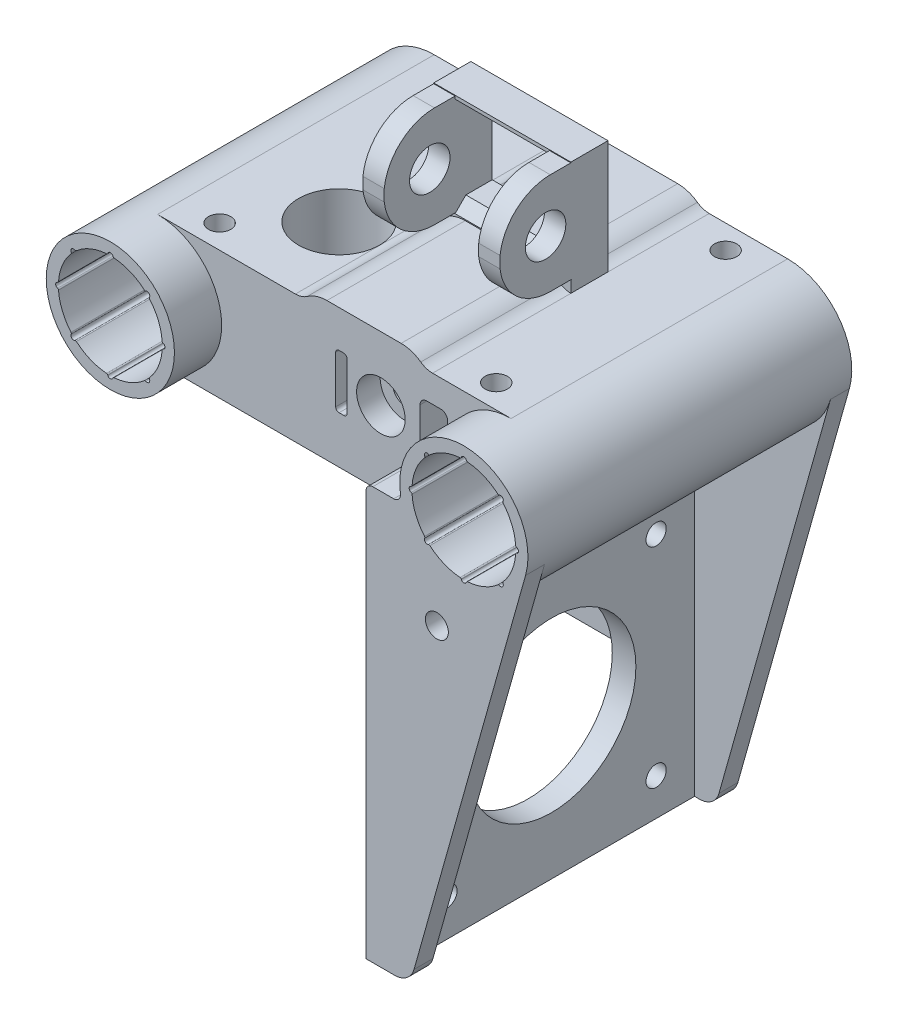
SolidWorks part; units mm, degrees
material "PET"
ref_plane "Front Plane" through (0, 0, 0) normal (0, 0, 1) x (1, 0, 0)
ref_plane "Top Plane" through (0, 0, 0) normal (0, 1, 0) x (1, 0, 0)
ref_plane "Right Plane" through (0, 0, 0) normal (1, 0, 0) x (0, 0, -1)
sketch "Sketch1" plane through (0, 0, 0) normal (0, 0, 1) x (1, 0, 0)
  arc A14 (-5.825, 5.0358) -> (-7.6797, 0.5581) centre (0, 0) ccw
  arc A15 (46.575, 5.0358) -> (44.7203, 0.5581) centre (52.4, 0) ccw
  circle A16 centre (0, 0) radius 9.5
  circle A17 centre (52.4, 0) radius 9.5
  arc A18 (-7.8195, 0.3817) -> (-7.8195, -0.3817) centre (-7.7, 0) ccw
  arc A19 (-5.2593, 5.7991) -> (-5.7991, 5.2593) centre (-5.4447, 5.4447) ccw
  arc A20 (0.3817, 7.8195) -> (-0.3817, 7.8195) centre (0, 7.7) ccw
  arc A21 (5.7991, 5.2593) -> (5.2593, 5.7991) centre (5.4447, 5.4447) ccw
  arc A22 (7.8195, -0.3817) -> (7.8195, 0.3817) centre (7.7, 0) ccw
  arc A23 (-5.7991, -5.2593) -> (-5.2593, -5.7991) centre (-5.4447, -5.4447) ccw
  arc A24 (-0.3817, -7.8195) -> (0.3817, -7.8195) centre (0, -7.7) ccw
  arc A25 (5.2593, -5.7991) -> (5.7991, -5.2593) centre (5.4447, -5.4447) ccw
  arc A26 (44.5805, 0.3817) -> (44.5805, -0.3817) centre (44.7, 0) ccw
  arc A27 (47.1407, 5.7991) -> (46.6009, 5.2593) centre (46.9553, 5.4447) ccw
  arc A28 (52.7817, 7.8195) -> (52.0183, 7.8195) centre (52.4, 7.7) ccw
  arc A29 (58.1991, 5.2593) -> (57.6593, 5.7991) centre (57.8447, 5.4447) ccw
  arc A30 (60.2195, -0.3817) -> (60.2195, 0.3817) centre (60.1, 0) ccw
  arc A31 (46.6009, -5.2593) -> (47.1407, -5.7991) centre (46.9553, -5.4447) ccw
  arc A32 (52.0183, -7.8195) -> (52.7817, -7.8195) centre (52.4, -7.7) ccw
  arc A33 (57.6593, -5.7991) -> (58.1991, -5.2593) centre (57.8447, -5.4447) ccw
  arc A34 (51.8419, 7.6797) -> (47.3642, 5.825) centre (52.4, 0) ccw
  arc A35 (44.7203, -0.5581) -> (46.575, -5.0358) centre (52.4, 0) ccw
  arc A36 (57.4358, 5.825) -> (52.9581, 7.6797) centre (52.4, 0) ccw
  arc A37 (60.0797, 0.5581) -> (58.225, 5.0358) centre (52.4, 0) ccw
  arc A38 (58.225, -5.0358) -> (60.0797, -0.5581) centre (52.4, 0) ccw
  arc A39 (52.9581, -7.6797) -> (57.4358, -5.825) centre (52.4, 0) ccw
  arc A40 (47.3642, -5.825) -> (51.8419, -7.6797) centre (52.4, 0) ccw
  arc A41 (-7.6797, -0.5581) -> (-5.825, -5.0358) centre (0, 0) ccw
  arc A42 (-5.0358, -5.825) -> (-0.5581, -7.6797) centre (0, 0) ccw
  arc A43 (0.5581, -7.6797) -> (5.0358, -5.825) centre (0, 0) ccw
  arc A44 (5.825, -5.0358) -> (7.6797, -0.5581) centre (0, 0) ccw
  arc A45 (7.6797, 0.5581) -> (5.825, 5.0358) centre (0, 0) ccw
  arc A46 (5.0358, 5.825) -> (0.5581, 7.6797) centre (0, 0) ccw
  arc A47 (-0.5581, 7.6797) -> (-5.0358, 5.825) centre (0, 0) ccw
  arc A48 (58.1991, -5.2593) -> (58.225, -5.0358) centre (58.3763, -5.1666) cw
  arc A49 (57.6593, -5.7991) -> (57.4358, -5.825) centre (57.5666, -5.9763) ccw
  arc A50 (52.0183, -7.8195) -> (51.8419, -7.6797) centre (51.8274, -7.8792) ccw
  arc A51 (47.1407, -5.7991) -> (47.3642, -5.825) centre (47.2334, -5.9763) cw
  arc A52 (46.6009, -5.2593) -> (46.575, -5.0358) centre (46.4237, -5.1666) ccw
  arc A53 (60.2195, -0.3817) -> (60.0797, -0.5581) centre (60.2792, -0.5726) ccw
  arc A54 (60.2195, 0.3817) -> (60.0797, 0.5581) centre (60.2792, 0.5726) cw
  arc A55 (58.1991, 5.2593) -> (58.225, 5.0358) centre (58.3763, 5.1666) ccw
  arc A56 (57.6593, 5.7991) -> (57.4358, 5.825) centre (57.5666, 5.9763) cw
  arc A57 (44.5805, -0.3817) -> (44.7203, -0.5581) centre (44.5208, -0.5726) cw
  arc A58 (44.5805, 0.3817) -> (44.7203, 0.5581) centre (44.5208, 0.5726) ccw
  arc A59 (46.6009, 5.2593) -> (46.575, 5.0358) centre (46.4237, 5.1666) cw
  arc A60 (47.1407, 5.7991) -> (47.3642, 5.825) centre (47.2334, 5.9763) ccw
  arc A61 (52.0183, 7.8195) -> (51.8419, 7.6797) centre (51.8274, 7.8792) cw
  arc A62 (52.7817, 7.8195) -> (52.9581, 7.6797) centre (52.9726, 7.8792) ccw
  arc A63 (7.8195, -0.3817) -> (7.6797, -0.5581) centre (7.8792, -0.5726) ccw
  arc A64 (7.8195, 0.3817) -> (7.6797, 0.5581) centre (7.8792, 0.5726) cw
  arc A65 (5.7991, -5.2593) -> (5.825, -5.0358) centre (5.9763, -5.1666) cw
  arc A66 (5.2593, -5.7991) -> (5.0358, -5.825) centre (5.1666, -5.9763) ccw
  arc A67 (-0.3817, -7.8195) -> (-0.5581, -7.6797) centre (-0.5726, -7.8792) ccw
  arc A68 (-5.2593, -5.7991) -> (-5.0358, -5.825) centre (-5.1666, -5.9763) cw
  arc A69 (-5.7991, -5.2593) -> (-5.825, -5.0358) centre (-5.9763, -5.1666) ccw
  arc A70 (-7.8195, -0.3817) -> (-7.6797, -0.5581) centre (-7.8792, -0.5726) cw
  arc A71 (-7.8195, 0.3817) -> (-7.6797, 0.5581) centre (-7.8792, 0.5726) ccw
  arc A72 (5.7991, 5.2593) -> (5.825, 5.0358) centre (5.9763, 5.1666) ccw
  arc A73 (5.2593, 5.7991) -> (5.0358, 5.825) centre (5.1666, 5.9763) cw
  arc A74 (-5.7991, 5.2593) -> (-5.825, 5.0358) centre (-5.9763, 5.1666) cw
  arc A75 (-5.2593, 5.7991) -> (-5.0358, 5.825) centre (-5.1666, 5.9763) ccw
  arc A76 (-0.3817, 7.8195) -> (-0.5581, 7.6797) centre (-0.5726, 7.8792) cw
  arc A77 (0.3817, 7.8195) -> (0.5581, 7.6797) centre (0.5726, 7.8792) ccw
  arc A78 (0.3817, -7.8195) -> (0.5581, -7.6797) centre (0.5726, -7.8792) cw
  arc A79 (52.7817, -7.8195) -> (52.9581, -7.6797) centre (52.9726, -7.8792) cw
extrude "Boss-Extrude1" add sketch "Sketch1" along normal blind 48
sketch "Sketch29" plane through (0, 0, 0) normal (0, 0, -1) x (-1, 0, 0)
  line L6 (-52.4, 9.5) -> (-40.7637, 9.5)
  line L45 (9.5, -36.55) -> (9.5, 0)
  line L66 (-45.0149, -61.4114) -> (-61.5459, -2.5695)
  line L74 (-3.3, -49.35) -> (-31.9, -49.35)
  line L76 (-38.9, 4.5) -> (-38.9, -1.5)
  line L77 (-34.9, -52.35) -> (-34.9, -60.6)
  line L78 (-37.9, -63.6) -> (-42.1267, -63.6)
  line L80 (-43, -1.5) -> (-43, -1.3748)
  line L81 (-43, 1.3748) -> (-43, 4.5)
  line L82 (-39.9, 5.5) -> (-42, 5.5)
  line L83 (-20.4363, 9.5) -> (0, 9.5)
  line L84 (-39.9, -2.5) -> (-42, -2.5)
  line L101 (-36.1, 11) -> (-25.1, 11)
  circle A58 centre (-3.3, -36.55) radius 1.5
  circle A59 centre (-17.3, -36.55) radius 1.5
  arc A65 (0, 9.5) -> (9.5, 0) centre (0, 0) ccw
  arc A73 (-42.1267, -63.6) -> (-45.0149, -61.4114) centre (-42.1267, -60.6) cw
  arc A75 (9.5, -36.55) -> (-3.3, -49.35) centre (-3.3, -36.55) cw
  arc A87 (-31.9, -49.35) -> (-34.9, -52.35) centre (-31.9, -52.35) ccw
  arc A88 (-34.9, -60.6) -> (-37.9, -63.6) centre (-37.9, -60.6) cw
  arc A89 (-38.9, -1.5) -> (-39.9, -2.5) centre (-39.9, -1.5) cw
  arc A90 (-39.9, 5.5) -> (-38.9, 4.5) centre (-39.9, 4.5) cw
  arc A93 (-43, 4.5) -> (-42, 5.5) centre (-42, 4.5) cw
  arc A102 (-61.5459, -2.5695) -> (-43, -1.3748) centre (-52.4, 0) ccw
  arc A103 (-43, -1.5) -> (-42, -2.5) centre (-42, -1.5) ccw
  arc A104 (-43, 1.3748) -> (-52.4, 9.5) centre (-52.4, 0) ccw
  arc A127 (-36.1, 11) -> (-39.0148, 10.0625) centre (-36.1, 6) ccw
  arc A128 (-22.1852, 10.0625) -> (-25.1, 11) centre (-25.1, 6) ccw
  arc A129 (-22.1852, 10.0625) -> (-20.4363, 9.5) centre (-20.4363, 12.5) ccw
  arc A130 (-39.0148, 10.0625) -> (-40.7637, 9.5) centre (-40.7637, 12.5) cw
extrude "Boss-Extrude18" add sketch "Sketch29" against normal blind 3
sketch "Sketch36" plane through (0, 0, 3) normal (0, 0, 1) x (1, 0, 0)
  line L9 (38.9, 4.5) -> (38.9, -1.5)
  line L15 (39.9, -2.5) -> (42, -2.5)
  line L17 (43, -1.5) -> (43, -1.3748)
  line L19 (43, 1.3748) -> (43, 4.5)
  line L21 (42, 5.5) -> (39.9, 5.5)
  line L37 (0, -9.5) -> (52.4, -9.5)
  line L38 (0, 9.5) -> (20.4363, 9.5)
  line L40 (40.7637, 9.5) -> (52.4, 9.5)
  line L57 (36.1, 11) -> (25.1, 11)
  line L58 (26.4, 5) -> (26.4, -2)
  line L59 (27.6, -2.5) -> (26.9, -2.5)
  line L60 (28.1, 5) -> (28.1, -2)
  line L61 (27.6, 5.5) -> (26.9, 5.5)
  arc A19 (39.9, 5.5) -> (38.9, 4.5) centre (39.9, 4.5) ccw
  arc A25 (38.9, -1.5) -> (39.9, -2.5) centre (39.9, -1.5) ccw
  arc A26 (42, -2.5) -> (43, -1.5) centre (42, -1.5) ccw
  arc A27 (43, 4.5) -> (42, 5.5) centre (42, 4.5) ccw
  arc A67 (0, -9.5) -> (0, 9.5) centre (0, 0) ccw
  arc A68 (52.4, 9.5) -> (43, 1.3748) centre (52.4, 0) ccw
  arc A69 (43, -1.3748) -> (52.4, -9.5) centre (52.4, 0) ccw
  arc A81 (39.0148, 10.0625) -> (40.7637, 9.5) centre (40.7637, 12.5) ccw
  arc A82 (22.1852, 10.0625) -> (20.4363, 9.5) centre (20.4363, 12.5) cw
  arc A83 (22.1852, 10.0625) -> (25.1, 11) centre (25.1, 6) cw
  arc A84 (36.1, 11) -> (39.0148, 10.0625) centre (36.1, 6) cw
  circle A85 centre (33.1, 1.5) radius 1.7
  arc A86 (27.6, 5.5) -> (28.1, 5) centre (27.6, 5) cw
  arc A87 (26.9, 5.5) -> (26.4, 5) centre (26.9, 5) ccw
  arc A88 (28.1, -2) -> (27.6, -2.5) centre (27.6, -2) cw
  arc A89 (26.9, -2.5) -> (26.4, -2) centre (26.9, -2) cw
extrude "Boss-Extrude26" add sketch "Sketch36" along normal blind 38
sketch "Sketch14" plane through (0, -9.5, 0) normal (0, -1, 0) x (1, 0, 0)
  circle A2 centre (14.4, 28.5) radius 4.125
extrude "Boss-Extrude27" add sketch "Sketch14" along normal blind 4
sketch "Sketch34" plane through (0, 9.5, 0) normal (0, 1, 0) x (1, 0, 0)
  circle A4 centre (14.4, -28.5) radius 6
extrude "Cut-Extrude17" cut sketch "Sketch34" against normal blind 10
sketch "Sketch38" plane through (0, -0.5, 0) normal (0, 1, 0) x (1, 0, 0)
  circle A2 centre (14.5, -28.5) radius 2.15
extrude "Cut-Extrude18" cut sketch "Sketch38" against normal up to surface (13 mm away) up to face at (18.525, -13.5, 28.5)
sketch "Sketch39" plane through (0, 0, 3) normal (0, 0, 1) x (1, 0, 0)
  line L12 (41.4, -63.6) -> (37.9, -63.6)
  line L13 (37.9, -3.5) -> (37.9, -63.6)
  line L15 (38.9, -2.5) -> (42, -2.5)
  line L17 (41.4, -63.6) -> (41.4, -9.5)
  line L20 (41.4, -9.5) -> (52.4, -9.5)
  line L21 (43, -1.5) -> (43, -1.3748)
  arc A2 (37.9, -3.5) -> (38.9, -2.5) centre (38.9, -3.5) cw
  arc A4 (42, -2.5) -> (43, -1.5) centre (42, -1.5) ccw
  arc A6 (43, -1.3748) -> (52.4, -9.5) centre (52.4, 0) ccw
extrude "Boss-Extrude43" add sketch "Sketch39" along normal offset from surface (42.2 mm away) 2.8 up to face at (61.9, 0, 48)
sketch "Sketch7" plane through (0, 0, 45.2) normal (0, 0, 1) x (1, 0, 0)
  line L14 (37.9, -63.6) -> (42.1267, -63.6)
  line L18 (43, -1.3748) -> (43, -1.5)
  line L19 (45.0149, -61.4114) -> (61.5459, -2.5695)
  line L21 (37.9, -3.5) -> (37.9, -63.6)
  line L26 (38.9, -2.5) -> (42, -2.5)
  circle A4 centre (48.4, -15.6) radius 1.7
  arc A6 (42.1267, -63.6) -> (45.0149, -61.4114) centre (42.1267, -60.6) ccw
  arc A22 (38.9, -2.5) -> (37.9, -3.5) centre (38.9, -3.5) ccw
  arc A30 (42, -2.5) -> (43, -1.5) centre (42, -1.5) ccw
  arc A31 (43, -1.3748) -> (61.5459, -2.5695) centre (52.4, 0) ccw
extrude "Boss-Extrude44" add sketch "Sketch7" along normal up to surface (2.8 mm away) up to face at (61.9, 0, 48)
sketch "Sketch69" plane through (37.9, 0, 0) normal (-1, 0, 0) x (0, 0, 1)
  line L0 (3, -9.5) -> (3, -25)
  line L2 (3, -25) -> (18.5, -9.5)
  line L4 (18.5, -9.5) -> (3, -9.5)
extrude "Boss-Extrude42" add sketch "Sketch69" along normal blind 6.5 from offset 25
sketch "Sketch40" plane through (0, 0, 45.2) normal (0, 0, -1) x (-1, 0, 0)
  line L23 (-42.2, -12.85) -> (-41.4, -12.85)
  line L24 (-42.2, -18.15) -> (-41.4, -18.15)
  line L26 (-41.4, -12.85) -> (-41.4, -18.15)
  line L28 (-42.7, -13.35) -> (-42.7, -17.65)
  arc A10 (-42.2, -12.85) -> (-42.7, -13.35) centre (-42.2, -13.35) ccw
  arc A11 (-42.7, -17.65) -> (-42.2, -18.15) centre (-42.2, -17.65) ccw
extrude "Boss-Extrude45" add sketch "Sketch40" along normal blind 10
sketch "Sketch47" plane through (41.4, 0, 0) normal (1, 0, 0) x (0, 0, -1)
  circle A0 centre (-8.5, -15.55) radius 1.5
  circle A1 centre (-8.5, -15.55) radius 4
extrude "Boss-Extrude40" add sketch "Sketch47" along normal blind 1.4
sketch "Sketch20" plane through (41.4, 0, 0) normal (1, 0, 0) x (0, 0, -1)
  circle A0 centre (-8.5, -58.1) radius 1.5
  circle A1 centre (-39.5, -58.1) radius 1.5
  circle A2 centre (-8.5, -27.1) radius 1.5
  circle A3 centre (-24, -42.6) radius 12.5
  circle A5 centre (-8.5, -15.55) radius 1.5
extrude "Cut-Extrude19" cut sketch "Sketch20" against normal up to surface (3.5 mm away) up to face at (37.9, -25.5333, 30.6667)
sketch "Sketch43" plane through (0, 0, 41) normal (0, 0, 1) x (1, 0, 0)
  circle A1 centre (33.1, 1.5) radius 3.6
extrude "Cut-Extrude22" cut sketch "Sketch43" against normal blind 3.5
sketch "Sketch62" plane through (0, 0, 3) normal (0, 0, 1) x (1, 0, 0)
  line L4 (61.9, -54.1) -> (61.9, 0)
  line L5 (52.4, -63.6) -> (41.4, -63.6)
  line L6 (41.4, -63.6) -> (41.4, -9.5)
  line L7 (41.4, -9.5) -> (52.4, -9.5)
  arc A1 (52.4, -9.5) -> (61.9, 0) centre (52.4, 0) ccw
  arc A2 (52.4, -63.6) -> (61.9, -54.1) centre (52.4, -54.1) ccw
extrude "Cut-Extrude30" cut sketch "Sketch62" against normal blind 0.2
sketch "Sketch70" plane through (0, 0, 0) normal (0, 0, -1) x (-1, 0, 0)
  line L6 (-36.1, -5) -> (-25.1, -5)
  line L7 (-23.1, -3) -> (-23.1, 6)
  line L8 (-25.1, 8) -> (-36.1, 8)
  line L9 (-38.1, 6) -> (-38.1, -3)
  arc A1 (-38.1, 6) -> (-36.1, 8) centre (-36.1, 6) cw
  arc A3 (-25.1, 8) -> (-23.1, 6) centre (-25.1, 6) cw
  arc A5 (-23.1, -3) -> (-25.1, -5) centre (-25.1, -3) cw
  arc A6 (-36.1, -5) -> (-38.1, -3) centre (-36.1, -3) cw
extrude "Cut-Extrude33" cut sketch "Sketch70" against normal blind 25
sketch "Sketch66" plane through (0, 0, 25) normal (0, 0, -1) x (-1, 0, 0)
  line L1 (-26.9, 5.5) -> (-28.4, 5.5)
  line L2 (-26.4, 5) -> (-26.4, -2)
  line L3 (-26.9, -2.5) -> (-28.4, -2.5)
  line L4 (-28.9, 5) -> (-28.9, -2)
  arc A0 (-26.4, -2) -> (-26.9, -2.5) centre (-26.9, -2) cw
  arc A1 (-28.4, -2.5) -> (-28.9, -2) centre (-28.4, -2) cw
  arc A2 (-28.4, 5.5) -> (-28.9, 5) centre (-28.4, 5) ccw
  arc A3 (-26.9, 5.5) -> (-26.4, 5) centre (-26.9, 5) cw
extrude "Cut-Extrude32" cut sketch "Sketch66" against normal blind 8
sketch "Sketch72" plane through (0, 9.5, 0) normal (0, 1, 0) x (1, 0, 0)
  circle A0 centre (46.7, -37.5) radius 1.65
  circle A1 centre (46.7, -3.5) radius 1.65
  circle A2 centre (5.7, -3.5) radius 1.65
  circle A3 centre (5.7, -37.5) radius 1.65
extrude "Cut-Extrude34" cut sketch "Sketch72" against normal up to next
sketch "Sketch74" plane through (0, 9.5, 0) normal (0, 1, 0) x (1, 0, 0)
  line L0 (20.4363, -41) -> (20.4363, 0) construction
  line L5 (20.4363, -15) -> (40.7637, -15)
  line L6 (20.4363, -15) -> (20.4363, -31)
  line L7 (20.4363, -31) -> (40.7637, -31)
  line L8 (40.7637, -15) -> (40.7637, -31)
  line L9 (40.7637, -41) -> (40.7637, 0) construction
extrude "Boss-Extrude46" add sketch "Sketch74" along normal blind 16.85
sketch "Sketch75" plane through (0, 0, 31) normal (0, 0, 1) x (1, 0, 0)
  line L1 (23.6, 24.25) -> (37.6, 24.25)
  line L2 (23.6, 24.25) -> (23.6, 12.75)
  line L3 (23.6, 12.75) -> (37.6, 12.75)
  line L4 (37.6, 24.25) -> (37.6, 12.75)
extrude "Cut-Extrude35" cut sketch "Sketch75" against normal up to surface (16 mm away) up to face at (30.6, 14.251, 15)
sketch "Sketch76" plane through (40.7637, 0, 0) normal (1, 0, 0) x (0, 0, -1)
  line L0 (-23.55, 26.25) -> (-31, 26.25)
  line L1 (-23.55, 11.25) -> (-31, 11.25)
  line L3 (-31, 11.25) -> (-31, 17.8854)
  line L4 (-31, 19.6146) -> (-31, 26.25)
  arc A0 (-23.55, 26.25) -> (-31, 19.6146) centre (-23.55, 18.75) ccw
  circle A2 centre (-24.25, 18.75) radius 3
  arc A3 (-31, 17.8854) -> (-23.55, 11.25) centre (-23.55, 18.75) ccw
extrude "Cut-Extrude36" cut sketch "Sketch76" against normal up to surface (20.3274 mm away) up to face at (20.4363, 17.925, 23)
sketch "Sketch77" plane through (0, 0, 31) normal (0, 0, 1) x (1, 0, 0)
  line L3 (23.6, 11.25) -> (23.6, 26.25)
  line L4 (20.4363, 26.35) -> (40.7637, 26.35)
  line L6 (37.6, 26.25) -> (37.6, 11.25)
  line L12 (25.1, 11) -> (36.1, 11)
  line L22 (20.4363, 26.35) -> (20.4363, 26.25)
  line L23 (20.4363, 26.25) -> (23.6, 26.25)
  line L24 (40.7637, 26.35) -> (40.7637, 26.25)
  line L25 (20.4363, 11.25) -> (23.6, 11.25)
  line L29 (20.4363, 11.25) -> (20.4363, 9.5)
  line L30 (40.7637, 11.25) -> (40.7637, 9.5)
  line L31 (37.6, 11.25) -> (40.7637, 11.25)
  line L32 (37.6, 26.25) -> (40.7637, 26.25)
  arc A0 (25.1, 11) -> (22.1852, 10.0625) centre (25.1, 6) ccw
  arc A1 (39.0148, 10.0625) -> (36.1, 11) centre (36.1, 6) ccw
  arc A2 (39.0148, 10.0625) -> (40.7637, 9.5) centre (40.7637, 12.5) ccw
  arc A7 (20.4363, 9.5) -> (22.1852, 10.0625) centre (20.4363, 12.5) ccw
extrude "Cut-Extrude37" cut sketch "Sketch77" against normal blind 10.5
chamfer "Chamfer1" distance 1.6 angle 45 2 edges at (30.6, 24.25, 20.5) (30.6, 12.75, 20.5)
